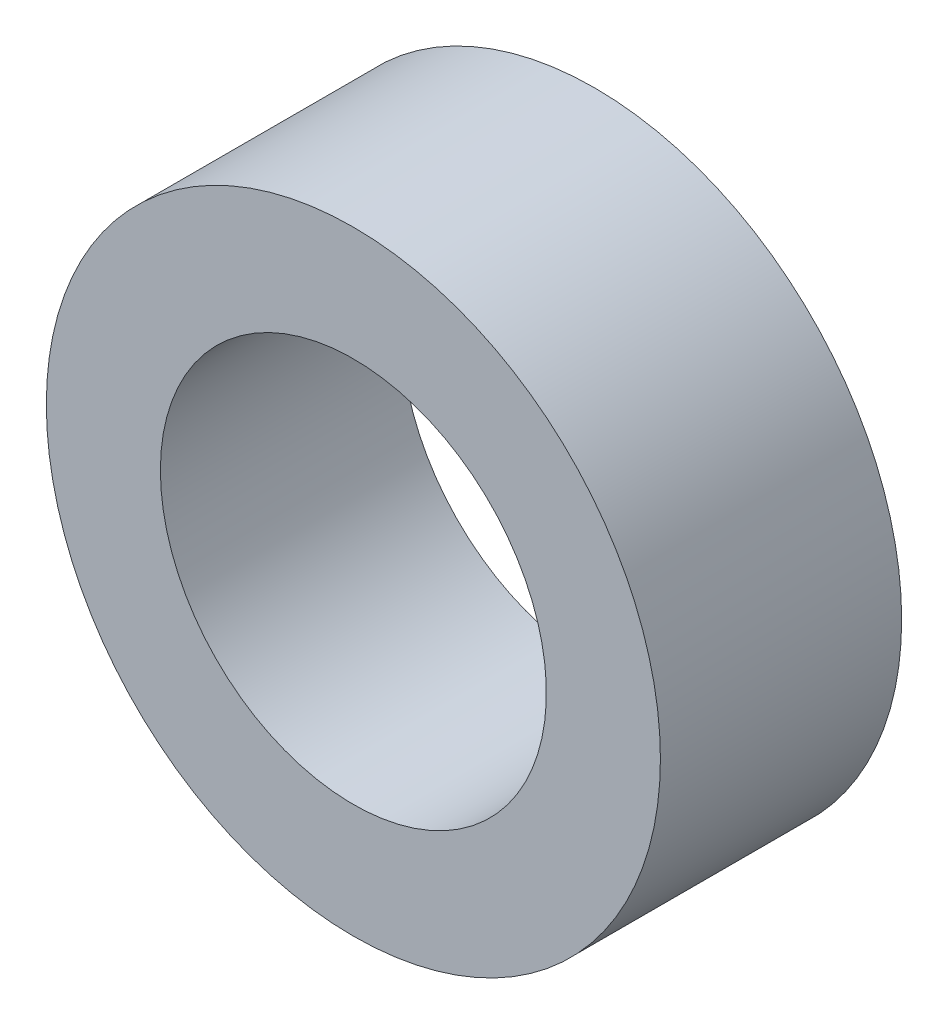
SolidWorks part; units mm, degrees
ref_plane "Front Plane" through (0, 0, 0) normal (0, 0, 1) x (1, 0, 0)
ref_plane "Top Plane" through (0, 0, 0) normal (0, 1, 0) x (1, 0, 0)
ref_plane "Right Plane" through (0, 0, 0) normal (1, 0, 0) x (0, 0, -1)
sketch "Sketch1" plane through (0, 0, 0) normal (0, 0, 1) x (1, 0, 0)
  circle A3 centre (0, 0) radius 4.4
  circle A6 centre (0, 0) radius 7
extrude "Boss-Extrude1" add sketch "Sketch1" along normal up to surface (5.5 mm away)
